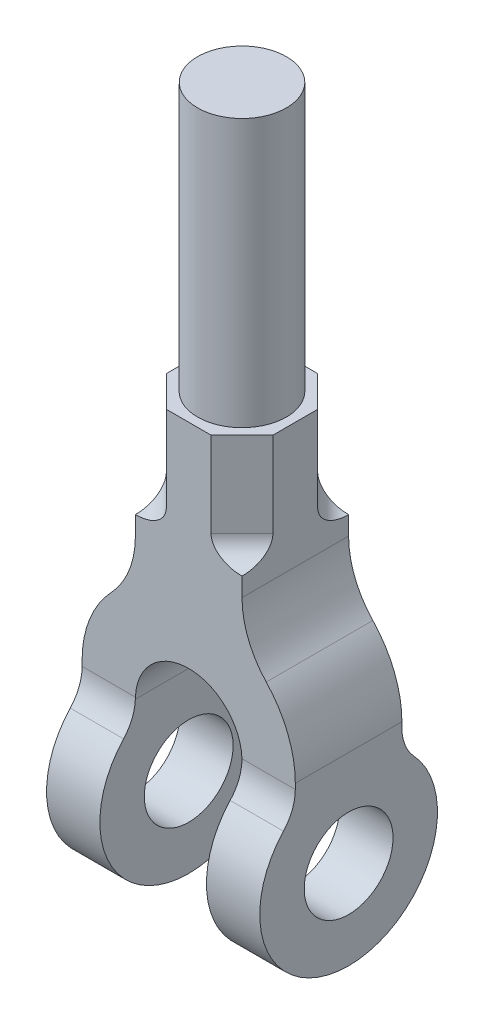
SolidWorks part; units mm, degrees
ref_plane "Front Plane" through (0, 0, 0) normal (0, 0, 1) x (1, 0, 0)
ref_plane "Top Plane" through (0, 0, 0) normal (0, 1, 0) x (1, 0, 0)
ref_plane "Right Plane" through (0, 0, 0) normal (1, 0, 0) x (0, 0, -1)
sketch "Sketch1" plane through (0, 0, 0) normal (0, 0, 1) x (1, 0, 0)
  line L1 (0, 0) -> (-120, 0)
  line L2 (0, 0) -> (0, 250)
  line L3 (0, 250) -> (-120, 250)
  line L4 (-120, 0) -> (-120, 250)
  dimension "D1" = 120
  dimension "D2" = 250
extrude "Boss-Extrude1" add sketch "Sketch1" along normal blind 100
sketch "Sketch2" plane through (0, 0, 100) normal (0, 0, 1) x (1, 0, 0)
  line L0 (-60, 250) -> (-60, 0) construction
  line L1 (0, 125) -> (-120, 125) construction
  line L2 (-90, 250) -> (-90, 179.4983)
  line L3 (-30, 250) -> (-30, 179.4983)
  line L4 (0, 0) -> (0, 250)
  line L5 (0, 250) -> (-120, 250)
  line L6 (-120, 250) -> (-120, 0)
  line L7 (-120, 0) -> (0, 0)
  line L8 (0, 0) -> (0, 250)
  line L9 (0, 250) -> (-120, 250)
  line L10 (-120, 250) -> (-120, 0)
  line L11 (-120, 0) -> (0, 0)
  line L12 (-90, 100) -> (-90, 0)
  line L13 (-30, 100) -> (-30, 0)
  arc A0 (-30, 100) -> (-90, 100) centre (-60, 100) ccw
  arc A1 (-103.6364, 145.1809) -> (-16.3636, 145.1809) centre (-60, 104) ccw
  arc A2 (-30, 179.4983) -> (-16.3636, 145.1809) centre (20, 179.4983) ccw
  arc A3 (-90, 179.4983) -> (-103.6364, 145.1809) centre (-140, 179.4983) cw
  point P17 (-30, 155.9615)
  point P20 (-90, 155.9615)
  line M13 (0, 250) -> (-120, 250)
  line M14 (-120, 250) -> (-120, 0)
  dimension "D2" = 120
  dimension "D3" = 60
  dimension "D7" = 50
  dimension "D4" = 4
  dimension "D5" = 150
  dimension "D6" = 30
  dimension "D1" = 0
extrude "Cut-Extrude1" cut sketch "Sketch2" against normal through all contours A3 L2 A1 M13 M14 | L3 A2 A1 L8 M13 | L12 A1 L13 A0 | A1 L12 L11 L13 region at (-106.1748, 195.5027, 100) region at (-13.8252, 195.5027, 100) region at (-60, 23.362, 100) region at (-60, 85.3374, 100)
sketch "Sketch3" plane through (0, 0, 0) normal (1, 0, 0) x (0, 0, -1)
  line L0 (-100, 0) -> (-100, 104) construction
  line L1 (-100, 0) -> (0, 0) construction
  line L2 (0, 0) -> (0, 104) construction
  line L3 (-50, 50) -> (-50, 250) construction
  line L4 (0, 250) -> (-100, 250) construction
  line L5 (0, 104) -> (0, 145.1809) construction
  line L7 (-80, 100.9902) -> (-80, 250)
  line L8 (-80, 250) -> (-20, 250)
  line L9 (-20, 100.9902) -> (-20, 250)
  line L10 (0, 145.1809) -> (0, 179.4983) construction
  line L11 (0, 250) -> (0, 179.4983) construction
  line L12 (-100, 179.4983) -> (-100, 145.1809) construction
  line L13 (-100, 145.1809) -> (-100, 104) construction
  line L14 (-100, 0) -> (0, 0)
  line L15 (0, 104) -> (0, 145.1809)
  line L16 (0, 145.1809) -> (0, 179.4983)
  line L17 (0, 250) -> (0, 179.4983)
  line L18 (-100, 179.4983) -> (-100, 145.1809)
  line L19 (-100, 145.1809) -> (-100, 104)
  line L20 (-100, 0) -> (-100, 104)
  line L21 (0, 0) -> (0, 104)
  line L22 (-100, 250) -> (-100, 179.4983) construction
  line L23 (0, 250) -> (-100, 250)
  line L24 (-100, 250) -> (-100, 179.4983)
  arc A0 (-86.6667, 83.9935) -> (-13.3333, 83.9935) centre (-50, 50) ccw
  circle A1 centre (-50, 50) radius 25
  arc A2 (-86.6667, 83.9935) -> (-80, 100.9902) centre (-105, 100.9902) ccw
  arc A3 (-13.3333, 83.9935) -> (-20, 100.9902) centre (5, 100.9902) cw
  line M10 (0, 0) -> (0, 104)
  line M11 (0, 104) -> (-100, 104)
  line M12 (-100, 104) -> (-100, 0)
  line M13 (-100, 0) -> (0, 0)
  dimension "D1" = 50
  dimension "D3" = 25
  dimension "D2" = 60
extrude "Cut-Extrude2" cut sketch "Sketch3" against normal through all contours L23 L24 L18 L19 L7 M11 | A0 A2 L7 M11 M12 | A0 L20 M13 | A0 L14 M10 | L17 L23 L9 L15 L16 M11 | A3 A0 L21 L9 M11 | A1 region at (0, 89.2915, 92.2772) region at (0, 177, 90) region at (0, 89.2915, 7.7228) region at (0, 177, 10) region at (0, 11.1684, 88.8316) region at (0, 11.1684, 11.1684) region at (0, 50, 50)
sketch "Sketch4" plane through (0, 250, 0) normal (0, 1, 0) x (1, 0, 0)
  line L0 (-90, -80) -> (-30, -20) construction
  line L1 (-90, -20) -> (-30, -80) construction
  line L2 (-90, -80) -> (-72.6, -80)
  line L3 (-72.6, -80) -> (-90, -62.6)
  line L4 (-30, -20) -> (-90, -20)
  line L5 (-90, -20) -> (-90, -80)
  line L6 (-90, -80) -> (-30, -80)
  line L7 (-30, -80) -> (-30, -20)
  line L8 (-30, -20) -> (-90, -20)
  line L9 (-90, -20) -> (-90, -80)
  line L10 (-90, -80) -> (-30, -80)
  line L11 (-30, -80) -> (-30, -20)
  line L12 (-90, -62.6) -> (-90, -80)
  line L13 (-90, -20) -> (-90, -80) construction
  line L14 (-90, -20) -> (-90, -37.4)
  line L15 (-90, -37.4) -> (-72.6, -20)
  line L16 (-30, -20) -> (-90, -20)
  line L17 (-30, -20) -> (-47.4, -20)
  line L18 (-47.4, -20) -> (-30, -37.4)
  line L19 (-30, -80) -> (-30, -20)
  line L20 (-30, -80) -> (-30, -62.6)
  line L21 (-30, -62.6) -> (-47.4, -80)
  line L22 (-90, -80) -> (-30, -80)
  circle A0 centre (-60, -50) radius 25
  point P26 (-60, -50)
  line M7 (-30, -20) -> (-90, -20)
  line M8 (-90, -20) -> (-90, -80)
  line M9 (-90, -80) -> (-30, -80)
  line M10 (-30, -80) -> (-30, -20)
  dimension "D2" = 50
  dimension "D3" = 17.4
  dimension "D4" = 17.4
  dimension "D5" = 4
  dimension "D1" = 0
extrude "Cut-Extrude3" cut sketch "Sketch4" against normal blind 60 contours L21 L10 M10 | L3 M9 M8 | L15 L8 M8 | L18 L11 M7 region at (-84.2, 250, 74.2) region at (-35.8, 250, 74.2) region at (-84.2, 250, 25.8) region at (-35.8, 250, 25.8)
extrude "Boss-Extrude2" add sketch "Sketch4<3>" along normal blind 150.7 contours A0 region at (-60, 250, 50)
sketch "Sketch4<3>" plane through (0, 250, 0) normal (0, 1, 0) x (1, 0, 0) same geometry as "Sketch4"
fillet "Fillet2" radius 12 4 edges at (-81.3, 190, 71.3) (-38.7, 190, 71.3) (-38.7, 190, 28.7) (-81.3, 190, 28.7)
